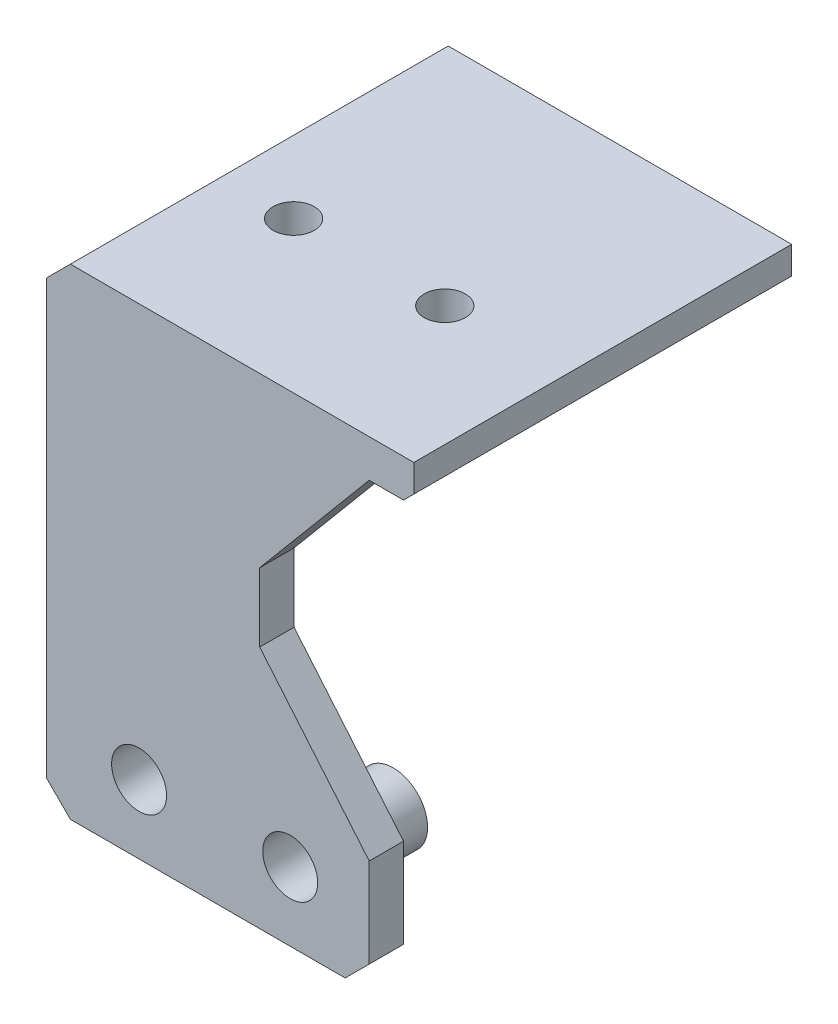
SolidWorks part; units mm, degrees
material "ABS"
ref_plane "Front Plane" through (0, 0, 0) normal (0, 0, 1) x (1, 0, 0)
ref_plane "Top Plane" through (0, 0, 0) normal (0, 1, 0) x (1, 0, 0)
ref_plane "Right Plane" through (0, 0, 0) normal (1, 0, 0) x (0, 0, -1)
sketch "Sketch1" plane through (0, 0, 0) normal (0, 0, 1) x (1, 0, 0)
  line L3 (43.5, -66.5) -> (40, -70)
  line L21 (0, -42.1329) -> (0, 6.1452) construction
  line L22 (50, 0) -> (0, 0)
  line L23 (50, -4) -> (50, 0)
  line L24 (48.5, -5.5) -> (50, -4)
  line L25 (43.5, -5.5) -> (48.5, -5.5)
  line L26 (27.5571, -24.5) -> (43.5, -5.5)
  line L27 (27.5571, -34.5) -> (27.5571, -24.5)
  line L28 (43.5, -53.5) -> (27.5571, -34.5)
  line L29 (40, -70) -> (43.5, -66.5)
  line L30 (43.5, -66.5) -> (43.5, -53.5)
  line L31 (0, 0) -> (-3.5, -3.5)
  line L32 (-3.5, -3.5) -> (-3.5, -66.5)
  line L33 (-3.5, -66.5) -> (0, -70)
  line L34 (0, -70) -> (40, -70)
  dimension "D1" = 63
  dimension "D2" = 48
  dimension "D3" = 50
  dimension "D4" = 130
  dimension "D5" = 10
  dimension "D6" = 70
  dimension "D7" = 135
  dimension "D8" = 135
  dimension "D9" = 135
  dimension "D10" = 4
  dimension "D11" = 13
  dimension "D12" = 5
  dimension "D13" = 53.5
  dimension "D14" = 1.5
extrude "Boss-Extrude1" add sketch "Sketch1" along normal blind 5 contours L21 L34 L3 L30 L28 L27 L26 L25 L24 L23 L22 | L33 L21 L31 L32 region at (17.5651, -35.4277, 0)
sketch "Sketch4" plane through (0, 0, 0) normal (0, 0, -1) x (-1, 0, 0)
  line L0 (-50, 0) -> (-50, -4)
  line L1 (-50, -4) -> (-45.5, -8.5)
  line L2 (-48.5, -5.5) -> (-50, -4) construction
  line L3 (-45.5, -8.5) -> (3.5, -8.5)
  line L4 (3.5, -3.5) -> (3.5, -66.5) construction
  line L5 (3.5, -8.5) -> (3.5, -3.5)
  line L6 (3.5, -3.5) -> (0, 0)
  line L7 (0, 0) -> (-50, 0)
  dimension "D1" = 5
extrude "Boss-Extrude2" add sketch "Sketch4" along normal blind 50
sketch "Sketch5" plane through (0, -8.5, 0) normal (0, -1, 0) x (1, 0, 0)
  line L1 (-3.5, -50) -> (-3.5, 0) construction
  line L2 (0, 5) -> (40, 5) construction
  circle A0 centre (32.5, -17) radius 3
  circle A1 centre (10.5, -17) radius 3
  circle A2 centre (10.5, -17) radius 5
  circle A3 centre (32.5, -17) radius 5
  dimension "D1" = 6
  dimension "D2" = 14
  dimension "D3" = 22
  dimension "D4" = 22
  dimension "D5" = 10
extrude "Cut-Extrude1" cut sketch "Sketch5" against normal through all contours A0 | A1
sketch "Sketch6" plane through (0, 0, 0) normal (0, 0, -1) x (-1, 0, 0)
  line L2 (3.5, -8.5) -> (3.5, -66.5) construction
  line L3 (0, 0) -> (-50, 0) construction
  circle A0 centre (-10, -60) radius 5
  circle A1 centre (-32, -60) radius 5
  circle A2 centre (-10, -60) radius 4
  circle A3 centre (-32, -60) radius 4
  dimension "D1" = 13.5
  dimension "D2" = 22
  dimension "D3" = 60
  dimension "D4" = 10
  dimension "D5" = 8
extrude "Boss-Extrude3" add sketch "Sketch6" along normal blind 10 contours A2 | A3 | A1 | A0 region at (10, -60, 0) region at (32, -60, 0)
extrude "Cut-Extrude2" cut sketch "Sketch5<3>" against normal blind 4 contours A2 A1 | A3 A0 region at (5.6414, -8.5, -17) region at (27.6414, -8.5, -17)
sketch "Sketch5<3>" plane through (0, -8.5, 0) normal (0, -1, 0) x (1, 0, 0) same geometry as "Sketch5"
sketch "Esquisse1" plane through (0, 0, 0) normal (0, 0, 1) x (1, 0, 0)
  circle A0 centre (10, -60) radius 4
  circle A1 centre (32, -60) radius 4
  dimension "D1" = 8
extrude "Enlèv. mat.-Extru.1" cut sketch "Esquisse1" along normal through all
